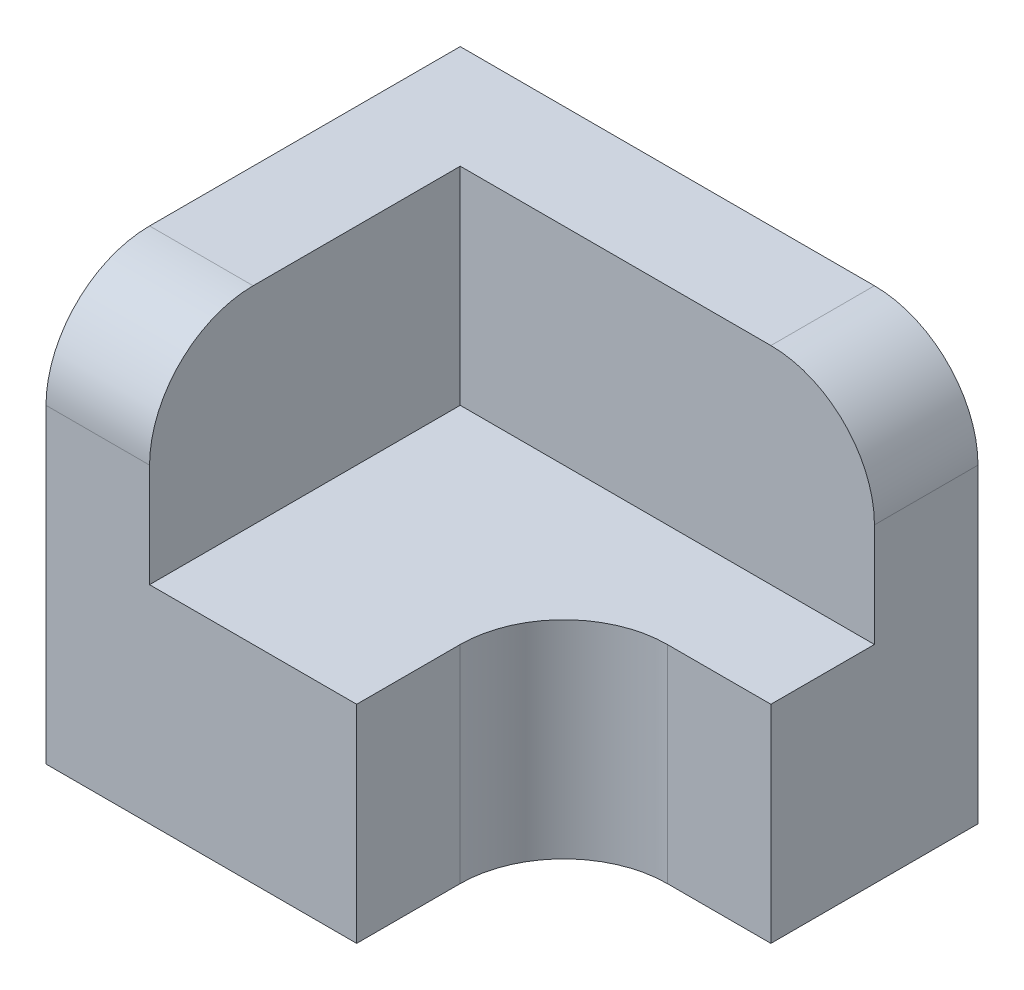
SolidWorks part; units mm, degrees
ref_plane "前基準面" through (0, 0, 0) normal (0, 0, 1) x (1, 0, 0)
ref_plane "上基準面" through (0, 0, 0) normal (0, 1, 0) x (1, 0, 0)
ref_plane "右基準面" through (0, 0, 0) normal (1, 0, 0) x (0, 0, -1)
sketch "草圖1" plane through (0, 0, 0) normal (0, 1, 0) x (1, 0, 0)
  line L1 (-12.5, -10) -> (12.5, -10)
  line L2 (-12.5, -10) -> (-12.5, 10)
  line L3 (-12.5, 10) -> (12.5, 10)
  line L4 (12.5, -10) -> (12.5, 10)
  line L5 (-12.5, -10) -> (12.5, 10) construction
  line L6 (-12.5, 10) -> (12.5, -10) construction
  line L7 (-12.5, -10) -> (-7.5, -10)
  line L8 (-12.5, -10) -> (-12.5, 10)
  line L9 (-12.5, 10) -> (-7.5, 10)
  line L10 (-7.5, -10) -> (-7.5, 5)
  line L11 (-12.5, 10) -> (12.5, 10)
  line L12 (-12.5, 10) -> (-12.5, 5)
  line L13 (-7.5, 5) -> (12.5, 5)
  line L14 (12.5, 10) -> (12.5, 5)
  line L15 (12.5, -10) -> (2.5, -10)
  line L16 (12.5, -10) -> (12.5, 0)
  line L17 (12.5, 0) -> (7.5, 0)
  line L18 (2.5, -10) -> (2.5, -5)
  arc A0 (2.5, -5) -> (7.5, 0) centre (7.5, -5) cw
  point P0 (0, 0)
  dimension "D7" = 5
  dimension "D1" = 20
  dimension "D2" = 25
  dimension "D3" = 5
  dimension "D4" = 5
  dimension "D5" = 5
  dimension "D6" = 10
extrude "填料-伸長1" add sketch "草圖1" along normal blind 10 contours L18 A0 L17 L4 L13 L10 L1 | L10 L13 L4 L3 L8 L2 L1 region at (-12.1798, 0, 2.5) region at (0.0945, 0, 1.2465)
extrude "填料-伸長2" add sketch "草圖1<3>" along normal blind 20 contours L10 L13 L4 L3 L8 L2 L1 region at (-12.1798, 0, 2.5)
sketch "草圖1<3>" plane through (0, 0, 0) normal (0, 1, 0) x (1, 0, 0) same geometry as "草圖1"
fillet "圓角1" radius 5 2 edges at (-10, 20, 10) (12.5, 20, -7.5)
